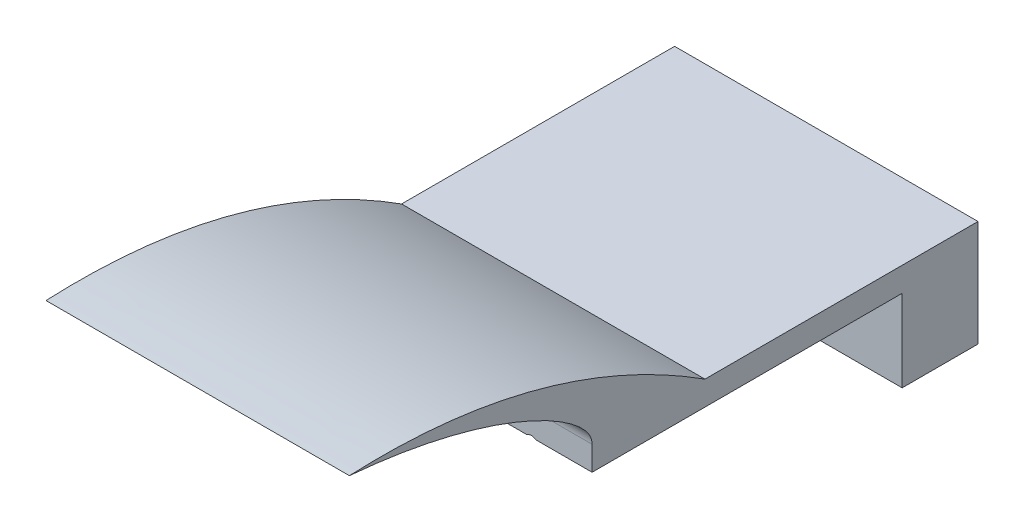
SolidWorks part; units mm, degrees
material "ABS"
ref_plane "Front Plane" through (0, 0, 0) normal (0, 0, 1) x (1, 0, 0)
ref_plane "Top Plane" through (0, 0, 0) normal (0, 1, 0) x (1, 0, 0)
ref_plane "Right Plane" through (0, 0, 0) normal (1, 0, 0) x (0, 0, -1)
curve "Curve1"
  spline degree 3 poles (0, 0.0012, 1.0003) (0, 0.0015, 0.9994) (0, 0.0028, 0.9958) (0, 0.0055, 0.9879) (0, 0.0099, 0.9747) (0, 0.0159, 0.9565) (0, 0.0233, 0.9333) (0, 0.0318, 0.9054) (0, 0.0411, 0.8731) (0, 0.051, 0.8366) (0, 0.0612, 0.7964) (0, 0.0713, 0.7528) (0, 0.0811, 0.7063) (0, 0.0903, 0.6574) (0, 0.0985, 0.6067) (0, 0.1057, 0.5546) (0, 0.1115, 0.5018) (0, 0.1158, 0.4488) (0, 0.1186, 0.3959) (0, 0.1189, 0.3436) (0, 0.1164, 0.2927) (0, 0.1112, 0.2442) (0, 0.1037, 0.1988) (0, 0.0942, 0.157) (0, 0.0831, 0.1194) (0, 0.0711, 0.0865) (0, 0.0584, 0.0585) (0, 0.0457, 0.0357) (0, 0.0334, 0.0184) (0, 0.0218, 0.0064) (0, 0.0108, -0.0005) (0, -0.0003, -0.0011) (0, -0.0092, 0.0055) (0, -0.0148, 0.017) (0, -0.0185, 0.0329) (0, -0.0204, 0.0533) (0, -0.0208, 0.0781) (0, -0.0198, 0.107) (0, -0.0176, 0.1398) (0, -0.0147, 0.176) (0, -0.0111, 0.2153) (0, -0.0074, 0.2574) (0, -0.0037, 0.3019) (0, -0.0005, 0.3484) (0, 0.002, 0.397) (0, 0.0037, 0.4471) (0, 0.0055, 0.4983) (0, 0.0069, 0.5496) (0, 0.0079, 0.6006) (0, 0.0085, 0.6505) (0, 0.0086, 0.699) (0, 0.0083, 0.7455) (0, 0.0076, 0.7894) (0, 0.0065, 0.8302) (0, 0.0053, 0.8675) (0, 0.0039, 0.9007) (0, 0.0027, 0.9296) (0, 0.0013, 0.9539) (0, 0.0006, 0.9727) (0, -0.0011, 0.9872) (0, 0, 0.9944) (0, -0.002, 0.9999) (0, -0.0005, 1) (0, 0, 1) knots 0 0 0 0 0.001372 0.005465 0.012235 0.021602 0.033461 0.047671 0.064081 0.082496 0.102719 0.124527 0.147676 0.171913 0.196978 0.222597 0.248497 0.274385 0.300041 0.32569 0.350525 0.37428 0.396711 0.417577 0.436654 0.453744 0.46868 0.481329 0.491631 0.499616 0.505546 0.510185 0.514824 0.520702 0.528516 0.538466 0.550543 0.564643 0.580638 0.598345 0.617584 0.638174 0.659922 0.682632 0.706121 0.730727 0.7557 0.780732 0.805564 0.829932 0.85357 0.876213 0.89761 0.917519 0.935698 0.951943 0.966047 0.97784 0.987174 0.993932 0.998018 0.999386 1 1 1 1
sketch "Sketch1" plane through (0, 0, 0) normal (1, 0, 0) x (0, 0, -1)
  line L1 (0.8093, 1.5275) -> (0.8093, -8.6325)
  line L3 (48.0533, 1.5275) -> (48.0533, -42.9225)
  line L4 (48.0533, -42.9225) -> (29.0033, -42.9225)
  line L5 (29.0033, -42.9225) -> (29.0033, -8.6325)
  line L6 (29.0033, -8.6325) -> (0.8093, -8.6325)
  line L8 (0.5507, 0) -> (-0.5507, 0) construction
  line L10 (0, 0.0768) -> (0, -0.0768) construction
  spline S0 degree 2 poles (-100.7907, 40.9362) (-19.4323, 44.7232) (48.0533, 1.5275) knots 0 0 0 1 1 1
  spline S1 degree 3 poles (-100.7907, 40.9362) (-95.812, 40.5065) (-85.4041, 39.3561) (-70.047, 36.8254) (-55.2045, 33.4552) (-41.8487, 29.54) (-30.1359, 25.2555) (-20.1921, 20.775) (-12.1117, 16.2715) (-5.9305, 11.9042) (-1.6817, 7.7681) (0.4919, 4.2872) (0.8118, 2.163) (0.8093, 1.5275) knots 0.353791 0.353791 0.353791 0.353791 0.37428 0.396711 0.417577 0.436654 0.453744 0.46868 0.481329 0.491631 0.499616 0.505546 0.508115 0.508115 0.508115 0.508115
  dimension "D2" = 1.5275
  dimension "D3" = 10.16
  dimension "D5" = 100.7907
  dimension "D6" = 47.244
  dimension "D7" = 44.45
  dimension "D8" = 34.29
  dimension "D9" = 19.05
  dimension "D10" = 29.1024
  dimension "D11" = 9.7768
  dimension "D12" = 48.0533
  dimension "D14" = 40.9362
extrude "Boss-Extrude1" add sketch "Sketch1" along normal mid plane 127
sketch "Sketch2" plane through (0, 0, -48.0533) normal (0, 0, -1) x (-1, 0, 0)
  line L0 (-63.5, -11.1725) -> (-38.1, -11.1725) construction
  line L1 (-63.5, -42.9225) -> (-63.5, 1.5275) construction
  line L2 (-38.1, -11.1725) -> (38.1, -11.1725) construction
  line L3 (38.1, -11.1725) -> (63.5, -11.1725) construction
  line L4 (63.5, -42.9225) -> (63.5, 1.5275) construction
  line L5 (-63.5, 1.5275) -> (63.5, 1.5275) construction
  circle A0 centre (-38.1, -11.1725) radius 3.175
  circle A1 centre (38.1, -11.1725) radius 3.175
  dimension "D1" = 6.35
  dimension "D2" = 25.4
  dimension "D3" = 12.7
extrude "Cut-Extrude1" cut sketch "Sketch2" against normal through all both and the other way through all
sketch "Sketch3" plane through (0, 0, -48.0533) normal (0, 0, -1) x (-1, 0, 0)
  line L4 (63.5, -42.9225) -> (63.5, 1.5275)
  line L5 (63.5, 1.5275) -> (-63.5, 1.5275)
  line L6 (-63.5, 1.5275) -> (-63.5, -42.9225)
  line L7 (-63.5, -42.9225) -> (63.5, -42.9225)
  line L8 (63.5, -42.9225) -> (63.5, 1.5275)
  line L9 (63.5, 1.5275) -> (-63.5, 1.5275)
  line L10 (-63.5, 1.5275) -> (-63.5, -42.9225)
  line L11 (-63.5, -42.9225) -> (63.5, -42.9225)
  circle A0 centre (-38.1, -11.1725) radius 3.175 construction
  circle A1 centre (-38.1, -11.1725) radius 3.175
  circle A2 centre (38.1, -11.1725) radius 3.175 construction
  circle A3 centre (38.1, -11.1725) radius 3.175
  dimension "D1" = 0
extrude "Boss-Extrude2" add sketch "Sketch3" along normal blind 114.3
sketch "Sketch4" plane through (-63.5, 0, 0) normal (-1, 0, 0) x (0, 0, 1)
  line L0 (-0.8093, -8.6325) -> (-29.0033, -8.6325) construction
  line L1 (-29.0033, -42.9225) -> (-130.6033, -42.9225)
  line L2 (-29.0033, -42.9225) -> (-29.0033, -8.6325)
  line L3 (-29.0033, -8.6325) -> (-130.6033, -8.6325)
  line L4 (-130.6033, -42.9225) -> (-130.6033, -8.6325)
  dimension "D1" = 101.6
extrude "Cut-Extrude2" cut sketch "Sketch4" against normal through all
